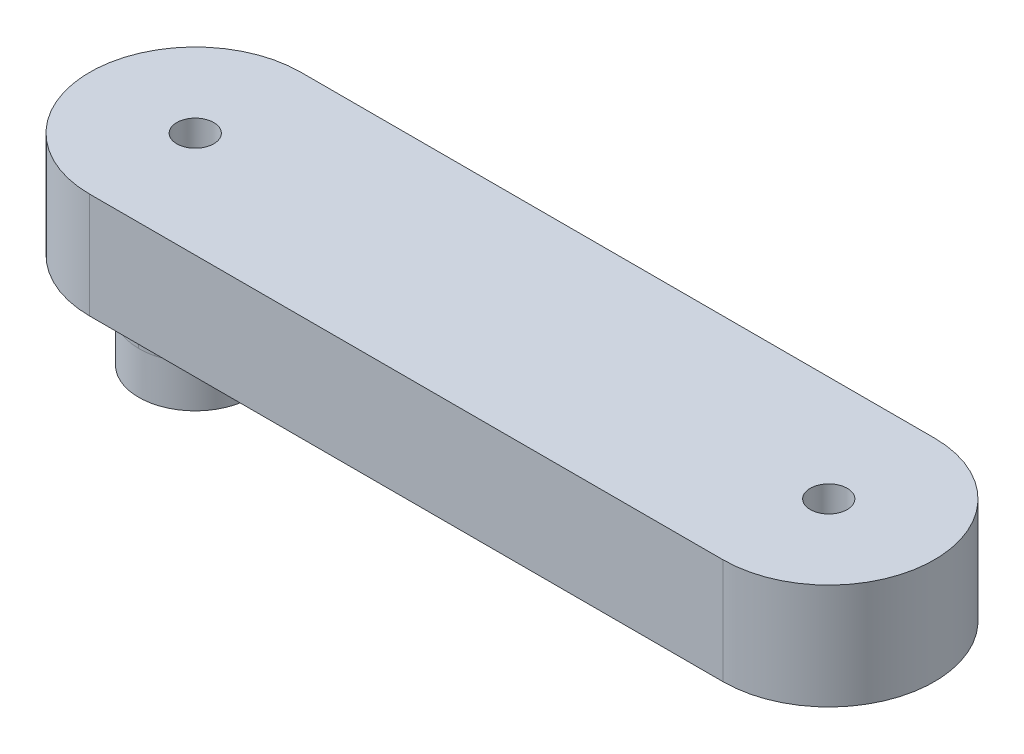
SolidWorks part; units mm, degrees
ref_plane "Front Plane" through (0, 0, 0) normal (0, 0, 1) x (1, 0, 0)
ref_plane "Top Plane" through (0, 0, 0) normal (0, 1, 0) x (1, 0, 0)
ref_plane "Right Plane" through (0, 0, 0) normal (1, 0, 0) x (0, 0, -1)
sketch "Sketch1" plane through (0, 0, 0) normal (0, 1, 0) x (1, 0, 0)
  line L0 (-30, 0) -> (30, 0) construction
  line L1 (-30, 10) -> (30, 10)
  line L2 (-30, -10) -> (30, -10)
  arc A0 (-30, 10) -> (-30, -10) centre (-30, 0) ccw
  arc A1 (30, -10) -> (30, 10) centre (30, 0) ccw
  point P3 (0, 0)
  dimension "D1" = 10
  dimension "D2" = 60
extrude "Boss-Extrude1" add sketch "Sketch1" along normal blind 10
sketch "Sketch2" plane through (0, 10, 0) normal (0, 1, 0) x (1, 0, 0)
  circle A5 centre (30, 0) radius 1.75
  dimension "D1" = 3.5
extrude "Cut-Extrude1" cut sketch "Sketch2" against normal up to next
sketch "Sketch5" plane through (0, 0, 0) normal (0, -1, 0) x (1, 0, 0)
  circle A0 centre (-30, 0) radius 5.35
  dimension "D1" = 10.7
extrude "Boss-Extrude3" add sketch "Sketch5" along normal blind 9
fillet "Fillet1" radius 5 1 edges at (-30, 0, 5.35)
sketch "Sketch6" plane through (0, -9, 0) normal (0, -1, 0) x (-1, 0, 0)
  circle A0 centre (30, 0) radius 1.75
  dimension "D1" = 3.5
extrude "Cut-Extrude2" cut sketch "Sketch6" against normal up to next
equation "\"Length\" = 60mm"
equation "\"Radius\"= 10mm"
equation "\"D1@Sketch1\"= \"Radius\""
equation "\"D2@Sketch1\" = \"Length\""
equation "\"Thick\"= 10mm"
equation "\"D1@Boss-Extrude1\"= \"Thick\""
